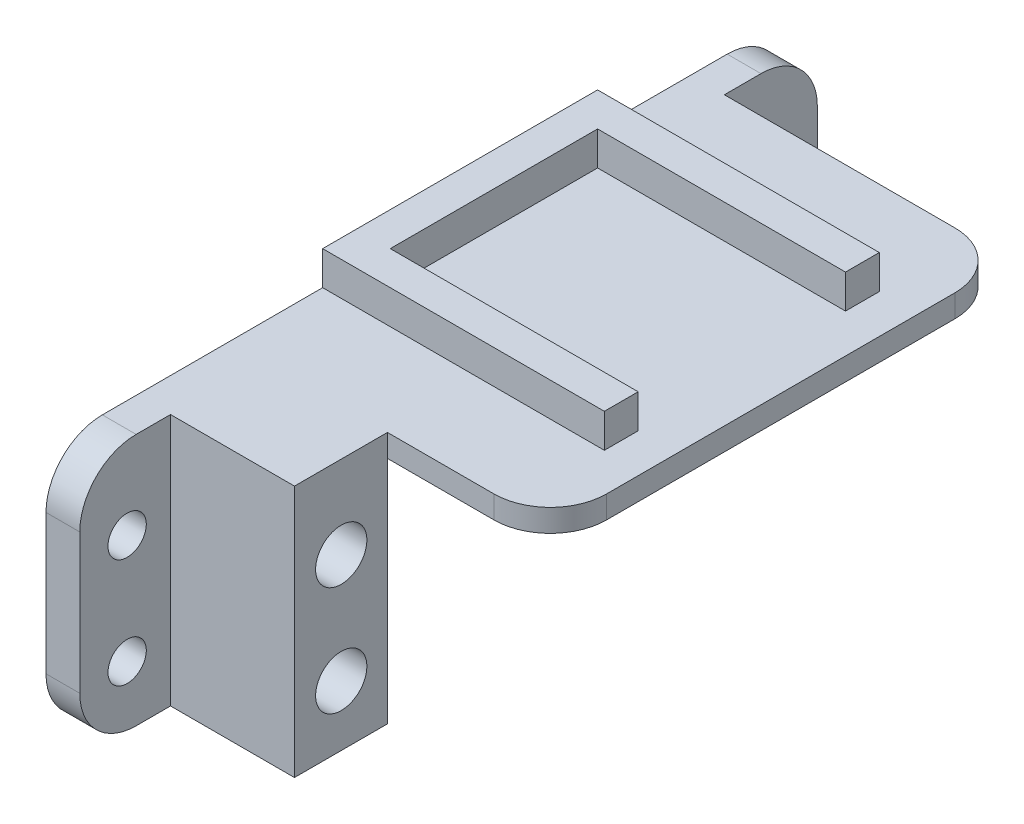
SolidWorks part; units mm, degrees
ref_plane "Front Plane" through (0, 0, 0) normal (0, 0, 1) x (1, 0, 0)
ref_plane "Top Plane" through (0, 0, 0) normal (0, 1, 0) x (1, 0, 0)
ref_plane "Right Plane" through (0, 0, 0) normal (1, 0, 0) x (0, 0, -1)
sketch "Sketch1" plane through (0, 0, 0) normal (0, 1, 0) x (1, 0, 0)
  line L0 (22.375, 20.45) -> (-6.075, 20.45)
  line L1 (-22.375, 28.7) -> (22.375, 28.7)
  line L2 (-22.375, 28.7) -> (-22.375, -28.7)
  line L3 (-22.375, -28.7) -> (22.375, -28.7)
  line L4 (22.375, 28.7) -> (22.375, -28.7)
  line L5 (-22.375, 28.7) -> (22.375, -28.7) construction
  line L6 (-22.375, -28.7) -> (22.375, 28.7) construction
  line L7 (-6.075, 20.45) -> (-6.075, 28.7)
  line L8 (22.375, -20.45) -> (-6.075, -20.45)
  line L9 (-6.075, -20.45) -> (-6.075, -28.7)
  line L10 (-6.075, -20.45) -> (-6.075, 20.45)
  line L11 (7.925, -20.45) -> (7.925, -28.7)
  line L12 (22.375, -28.7) -> (24.375, -28.7)
  line L13 (22.375, -28.7) -> (22.375, 28.7)
  line L14 (22.375, 28.7) -> (24.375, 28.7)
  line L15 (24.375, -28.7) -> (24.375, 28.7)
  line L16 (22.375, -20.45) -> (24.375, -20.45)
  line L17 (7.925, 28.7) -> (7.925, 20.45)
  line L18 (-3.075, 28.7) -> (-3.075, 20.45)
  point P0 (0, 0)
  point P11 (-6.075, 0)
  dimension "D1" = 28.45
  dimension "D2" = 16.3
  dimension "D3" = 40.9
  dimension "D4" = 57.4
  dimension "D5" = 2
  dimension "D6" = 14
  dimension "D7" = 3
extrude "Boss-Extrude1" add sketch "Sketch1" along normal blind 2 contours L10 L8 L4 L0 | L11 L8 L9 L3 | L18 L1 L7 L0 region at (8.15, 0, 0) region at (-4.575, 0, -24.575) region at (0.925, 0, 24.575)
extrude "Boss-Extrude2" add sketch "Sketch1<3>" against normal blind 20.4 contours L11 L8 L9 L3 | L18 L1 L7 L0 region at (-4.575, 0, -24.575) region at (0.925, 0, 24.575)
sketch "Sketch1<3>" plane through (0, 0, 0) normal (0, 1, 0) x (1, 0, 0) same geometry as "Sketch1"
sketch "Sketch5" plane through (0, 0, 0) normal (1, 0, 0) x (0, 0, -1)
  line L1 (-28.7, 2) -> (-36.75, 2)
  line L2 (-28.7, 2) -> (-28.7, -20.4)
  line L3 (-28.7, -20.4) -> (-36.75, -20.4)
  line L4 (-36.75, 2) -> (-36.75, -20.4)
  line L5 (-28.7, 2) -> (-28.7, -20.4) construction
  line L6 (-20.45, -20.4) -> (-28.7, -20.4) construction
  line L7 (-28.7, 2) -> (28.7, 2) construction
  dimension "D1" = 8.05
extrude "Boss-Extrude4" add sketch "Sketch5" along normal blind 3 from surface starting at face at (-6.075, -9.7, 0)
sketch "Sketch2" plane through (0, 0, 0) normal (1, 0, 0) x (0, 0, -1)
  line L0 (24.55, -5.35) -> (24.55, -15.05) construction
  line L1 (-24.55, -5.35) -> (-24.55, -15.05) construction
  line L2 (-24.55, -10.2) -> (24.55, -10.2) construction
  line L3 (-28.7, 0) -> (28.7, 0) construction
  circle A0 centre (24.55, -15.05) radius 1.7
  circle A1 centre (-24.55, -15.05) radius 2.275
  circle A2 centre (-24.55, -5.35) radius 2.275
  circle A3 centre (24.55, -5.35) radius 1.7
  circle A4 centre (-32.55, -5.35) radius 1.7
  circle A5 centre (-32.55, -15.05) radius 1.7
  point P10 (24.55, -10.2)
  point P13 (0, -10.2)
  dimension "D4" = 4.55
  dimension "D5" = 4.55
  dimension "D6" = 3.4
  dimension "D7" = 3.4
  dimension "D9" = 3.4
  dimension "D10" = 3.4
  dimension "D1" = 9.7
  dimension "D2" = 49.1
  dimension "D3" = 10.2
  dimension "D8" = 8
extrude "Cut-Extrude1" cut sketch "Sketch2" along normal through all from surface starting at face at (-6.075, -9.7, 2.0125)
sketch "Sketch3" plane through (0, 0, 0) normal (0, 1, 0) x (1, 0, 0)
  line L0 (-3.575, 7) -> (-3.575, -7) construction
  line L1 (-6.075, -20.45) -> (-6.075, 20.45) construction
  line L2 (-6.075, 9.5) -> (-1.075, 9.5)
  line L3 (-6.075, 9.5) -> (-6.075, 4.5)
  line L4 (-6.075, 4.5) -> (-1.075, 4.5)
  line L5 (-1.075, 9.5) -> (-1.075, 4.5)
  line L6 (-6.075, 9.5) -> (-1.075, 4.5) construction
  line L7 (-6.075, 4.5) -> (-1.075, 9.5) construction
  line L8 (-6.075, -9.5) -> (-1.075, -9.5)
  line L9 (-6.075, -9.5) -> (-6.075, -4.5)
  line L10 (-6.075, -4.5) -> (-1.075, -4.5)
  line L11 (-1.075, -9.5) -> (-1.075, -4.5)
  line L12 (-6.075, -9.5) -> (-1.075, -4.5) construction
  line L13 (-6.075, -4.5) -> (-1.075, -9.5) construction
  line L14 (19.925, 9.5) -> (16.925, 9.5)
  line L15 (19.925, 9.5) -> (19.925, -9.5)
  line L16 (19.925, -9.5) -> (16.925, -9.5)
  line L17 (16.925, 9.5) -> (16.925, -9.5)
  line L18 (19.925, 9.5) -> (16.925, -9.5) construction
  line L19 (19.925, -9.5) -> (16.925, 9.5) construction
  line L20 (-1.075, 9.5) -> (16.925, 9.5)
  line L21 (-1.075, 4.5) -> (16.925, 0)
  line L22 (-1.075, -9.5) -> (16.925, -9.5)
  line L23 (-1.075, -4.5) -> (16.925, 0)
  circle A0 centre (-3.575, 7) radius 1.2
  circle A1 centre (-3.575, -7) radius 1.2
  point P4 (-3.575, 0)
  point P14 (18.425, 0)
  dimension "D2" = 2.4
  dimension "D3" = 2.4
  dimension "D1" = 14
  dimension "D4" = 5
  dimension "D5" = 5
  dimension "D7" = 5
  dimension "D8" = 3
  dimension "D9" = 22
fillet "Fillet1" radius 5 6 edges at (-4.575, -20.4, 36.75) (-4.575, 2, -28.7) (-4.575, 2, 36.75) (22.375, 1, -20.45) (22.375, 1, 20.45) (-4.575, -20.4, -28.7)
sketch "Sketch6" plane through (0, 0, 0) normal (0, 1, 0) x (1, 0, 0)
  line L0 (-6.075, -30.85) -> (-6.075, -34.25) construction
  line L1 (-6.075, 9.2) -> (-3.075, 9.2)
  line L2 (-6.075, 9.2) -> (-6.075, -9.2)
  line L3 (-6.075, -9.2) -> (-3.075, -9.2)
  line L4 (-3.075, 9.2) -> (-3.075, -9.2)
  line L5 (-6.075, 9.2) -> (-3.075, -9.2) construction
  line L6 (-6.075, -9.2) -> (-3.075, 9.2) construction
  line L8 (-6.075, -9.2) -> (18.925, -9.2)
  line L9 (-6.075, -9.2) -> (-6.075, -12.2)
  line L10 (-6.075, -12.2) -> (18.925, -12.2)
  line L11 (18.925, -9.2) -> (18.925, -12.2)
  line L12 (-6.075, 9.2) -> (18.925, 9.2)
  line L13 (-6.075, 9.2) -> (-6.075, 12.2)
  line L14 (-6.075, 12.2) -> (18.925, 12.2)
  line L15 (18.925, 9.2) -> (18.925, 12.2)
  point P0 (-4.575, 0)
  dimension "D1" = 18.4
  dimension "D2" = 3
  dimension "D3" = 3
  dimension "D4" = 3
  dimension "D5" = 25
extrude "Boss-Extrude5" add sketch "Sketch6" along normal blind 5 contours L12 L15 L14 L13 L1 | L4 L1 L2 L3 | L11 L8 L3 L9 L10 region at (6.425, 0, -10.7) region at (-4.575, 0, 0) region at (6.425, 0, 10.7)
